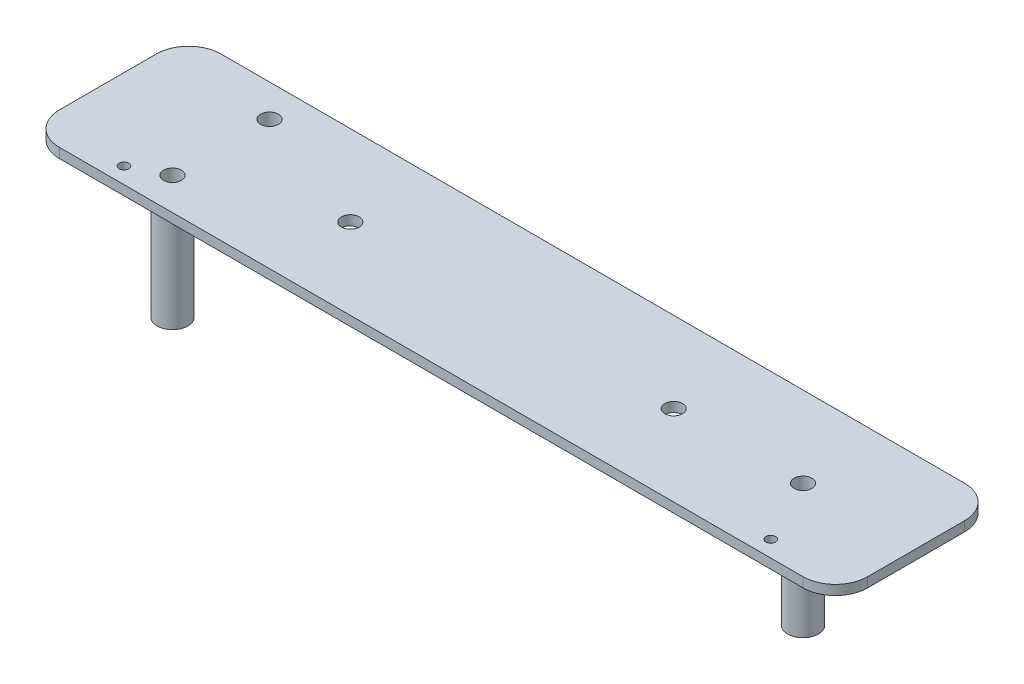
SolidWorks part; units mm, degrees
ref_plane "Front Plane" through (0, 0, 0) normal (0, 0, 1) x (1, 0, 0)
ref_plane "Top Plane" through (0, 0, 0) normal (0, 1, 0) x (1, 0, 0)
ref_plane "Right Plane" through (0, 0, 0) normal (1, 0, 0) x (0, 0, -1)
sketch "Sketch1" plane through (0, 0, 0) normal (0, 1, 0) x (1, 0, 0)
  line L0 (-90, 15) -> (90, 15) construction
  line L1 (-115, 25) -> (115, 25)
  line L2 (-125, 15) -> (-125, -15)
  line L3 (-115, -25) -> (115, -25)
  line L4 (125, 15) -> (125, -15)
  line L5 (-125, 25) -> (125, -25) construction
  line L6 (-125, -25) -> (125, 25) construction
  line L7 (90, 15) -> (90, 0) construction
  line L8 (0, 0) -> (0, -25) construction
  line L9 (-50, 0) -> (0, 0) construction
  circle A2 centre (90, 0) radius 2.75
  circle A3 centre (-90, 15) radius 2.75
  circle A4 centre (-50, 0) radius 2.75
  circle A6 centre (50, 0) radius 2.75
  circle A7 centre (-90, -15) radius 2.75
  arc A8 (115, 25) -> (125, 15) centre (115, 15) cw
  arc A9 (115, -25) -> (125, -15) centre (115, -15) ccw
  arc A10 (-125, -15) -> (-115, -25) centre (-115, -15) ccw
  arc A11 (-115, 25) -> (-125, 15) centre (-115, 15) ccw
  circle A12 centre (-100, -20) radius 1.5
  circle A13 centre (100, -20) radius 1.5
  point P0 (0, 0)
  point P12 (0, 15)
  dimension "D1" = 30
  dimension "D4" = 40
  dimension "D5" = 5.5
  dimension "D6" = 10
  dimension "D8" = 3
  dimension "D9" = 200
  dimension "D2" = 250
  dimension "D3" = 50
  dimension "D7" = 100
  dimension "D10" = 5
extrude "Boss-Extrude1" add sketch "Sketch1" along normal blind 3
sketch "Sketch2" plane through (0, 0, 0) normal (0, -1, 0) x (-1, 0, 0)
  line L0 (125, 0) -> (50, 0) construction
  line L1 (125, 15) -> (125, -15) construction
  circle A0 centre (90, -15) radius 4.75
  circle A1 centre (90, -15) radius 2.75
  circle A2 centre (90, 15) radius 4.75
  circle A3 centre (90, 15) radius 2.75
  circle A4 centre (90, -15) radius 2.75 construction
  circle A5 centre (-90, 0) radius 2.75
  circle A6 centre (-90, 0) radius 4.75
  circle A7 centre (-90, 0) radius 2.75 construction
  dimension "D1" = 2
extrude "Boss-Extrude2" add sketch "Sketch2" along normal blind 35
